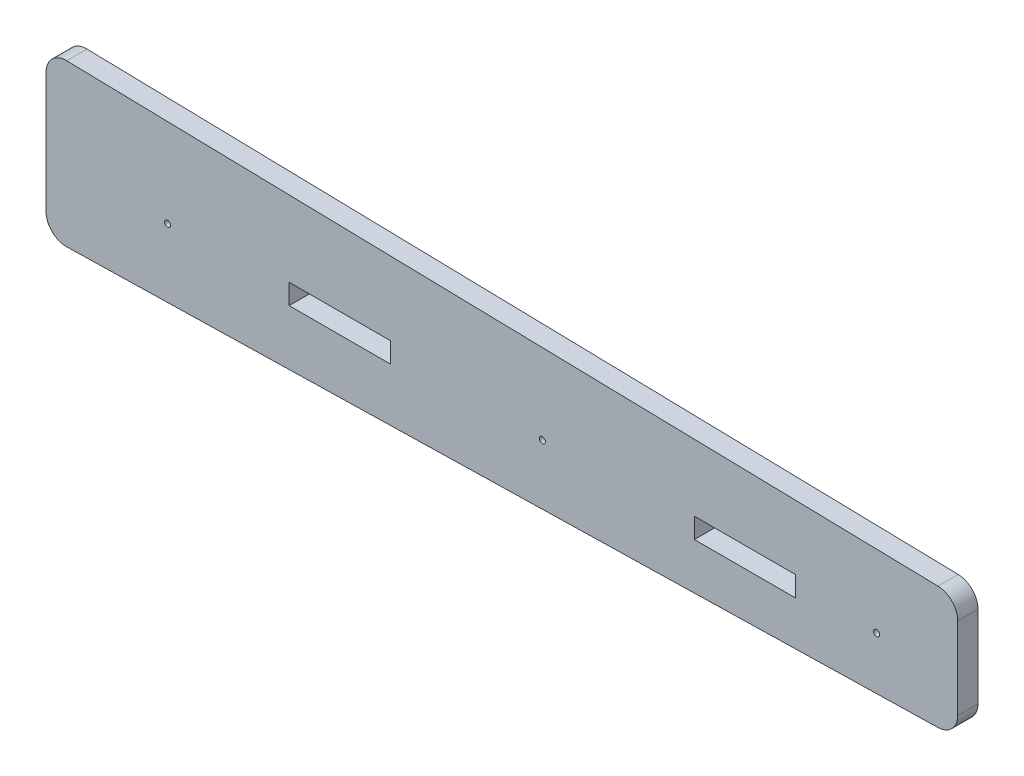
SolidWorks part; units mm, degrees
material "Teak"
ref_plane "Front Plane" through (0, 0, 0) normal (0, 0, 1) x (1, 0, 0)
ref_plane "Top Plane" through (0, 0, 0) normal (0, 1, 0) x (1, 0, 0)
ref_plane "Right Plane" through (0, 0, 0) normal (1, 0, 0) x (0, 0, -1)
sketch "Sketch1" plane through (0, 0, 0) normal (0, 0, 1) x (1, 0, 0)
  line L0 (-225, 40) -> (-225, -40)
  line L5 (-225, -40) -> (225, -30)
  line L6 (225, -30) -> (225, 30)
  line L7 (-105, 0) -> (-55, 0)
  line L8 (-105, 0) -> (-105, -10)
  line L9 (-105, -10) -> (-55, -10)
  line L10 (-55, 0) -> (-55, -10)
  line L11 (-105, 0) -> (-55, -10) construction
  line L12 (-105, -10) -> (-55, 0) construction
  line L13 (95, 0) -> (145, 0)
  line L14 (95, 0) -> (95, -10)
  line L15 (95, -10) -> (145, -10)
  line L16 (145, 0) -> (145, -10)
  line L17 (95, 0) -> (145, -10) construction
  line L18 (95, -10) -> (145, 0) construction
  line L19 (225, 30) -> (-225, 40)
  point P0 (0, 0)
  point P4 (-225, 0)
  point P11 (120, -5)
  point P17 (225, 0)
  point P22 (0, 35)
  point P26 (-80, -5)
  dimension "D1" = 50
  dimension "D2" = 10
  dimension "D3" = 60
  dimension "D4" = 80
  dimension "D5" = 450
  dimension "D6" = 150
  dimension "D7" = 80
  dimension "D8" = 5
extrude "Основа" add sketch "Sketch1" along normal blind 10
fillet "Fillet1" radius 10 4 edges at (-225, -40, 5) (-225, 40, 5) (225, -30, 5) (225, 30, 5)
sketch "Sketch2" plane through (0, 0, 10) normal (0, 0, 1) x (1, 0, 0)
  line L0 (-55, -10) -> (-55, 0) construction
  line L1 (145, -5) -> (225, -5) construction
  line L2 (145, -10) -> (145, 0) construction
  line L3 (225, -20.2198) -> (225, 20.2198) construction
  line L4 (95, -5) -> (-55, -5) construction
  line L5 (95, 0) -> (95, -10) construction
  line L6 (-105, -5) -> (-225, -5) construction
  line L7 (-105, 0) -> (-105, -10) construction
  line L8 (-225, 29.7753) -> (-225, -29.7753) construction
  circle A0 centre (-165, -5) radius 1.5
  circle A1 centre (20, -5) radius 1.5
  circle A2 centre (185, -5) radius 1.5
  point P9 (-55, -5)
  point P25 (185, -5)
  point P26 (20, -5)
  point P28 (-165, -5)
  dimension "D1" = 3
extrude "Под шурупы" cut sketch "Sketch2" against normal up to next
